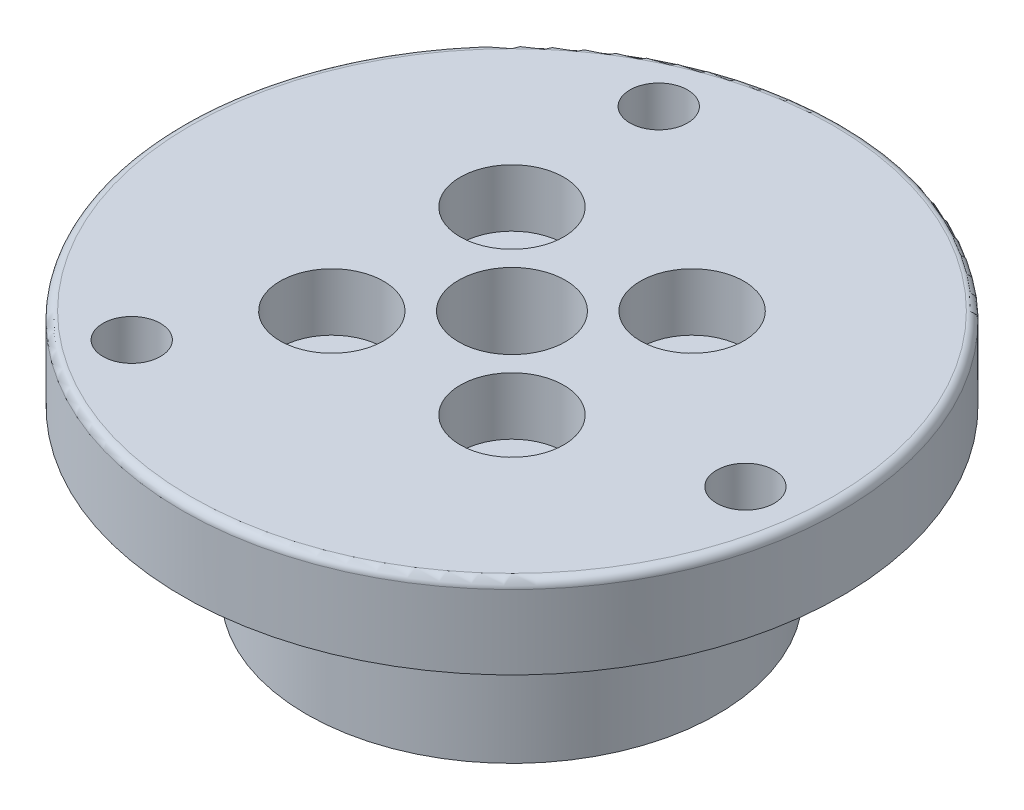
SolidWorks part; units mm, degrees
ref_plane "前基準面" through (0, 0, 0) normal (0, 0, 1) x (1, 0, 0)
ref_plane "上基準面" through (0, 0, 0) normal (0, 1, 0) x (1, 0, 0)
ref_plane "右基準面" through (0, 0, 0) normal (1, 0, 0) x (0, 0, -1)
sketch "Sketch1" plane through (0, 0, 0) normal (0, 1, 0) x (1, 0, 0)
  line L0 (0, 0) -> (-6.3143, 15.244) construction
  line L5 (-5.4801, 5.4801) -> (-5.4801, -5.4801) construction
  line L7 (0, 0) -> (0, 21.4212) construction
  circle A1 centre (0, 0) radius 3.25
  circle A2 centre (5.4801, 5.4801) radius 1.75
  circle A3 centre (5.4801, -5.4801) radius 1.75
  circle A4 centre (-5.4801, -5.4801) radius 1.75
  circle A5 centre (-5.4801, 5.4801) radius 1.75
  circle A6 centre (-10.0446, -13.0903) radius 1.75
  circle A7 centre (-6.3143, 15.244) radius 1.75
  circle A8 centre (16.3588, -2.1537) radius 1.75
  circle A9 centre (0, 0) radius 20.05
  point P15 (0, 0)
  point P25 (0, 0)
  dimension "D2" = 6.5
  dimension "D5" = 3.5
  dimension "D8" = 3.5
  dimension "D11" = 40.1
  dimension "D4" = 15.5
  dimension "D6" = 22.5
  dimension "D10" = 16.5
  dimension "D3" = 4
  dimension "D9" = 3
extrude "Extrude1" add sketch "Sketch1" along normal blind 15 contours A5 A4 A3 A2 A1 region at (-19.4829, 0, 0)
sketch "Sketch7" plane through (0, 15, 0) normal (0, 1, 0) x (1, 0, 0)
  circle A0 centre (-5.4801, 5.4801) radius 3.15
  circle A1 centre (5.4801, 5.4801) radius 3.15
  circle A2 centre (5.4801, -5.4801) radius 3.15
  circle A3 centre (-5.4801, -5.4801) radius 3.15
  dimension "D1" = 6.3
extrude "Extrude4" cut sketch "Sketch7" against normal blind 3.5
sketch "Sketch8" plane through (0, 0, 0) normal (0, -1, 0) x (1, 0, 0)
  circle A0 centre (0, 0) radius 20.05
  circle A1 centre (0, 0) radius 12.5
  dimension "D1" = 25
extrude "Extrude5" cut sketch "Sketch8" against normal blind 10
fillet "圓角1" radius 0.5 1 edges at (0, 15, 20.05)
